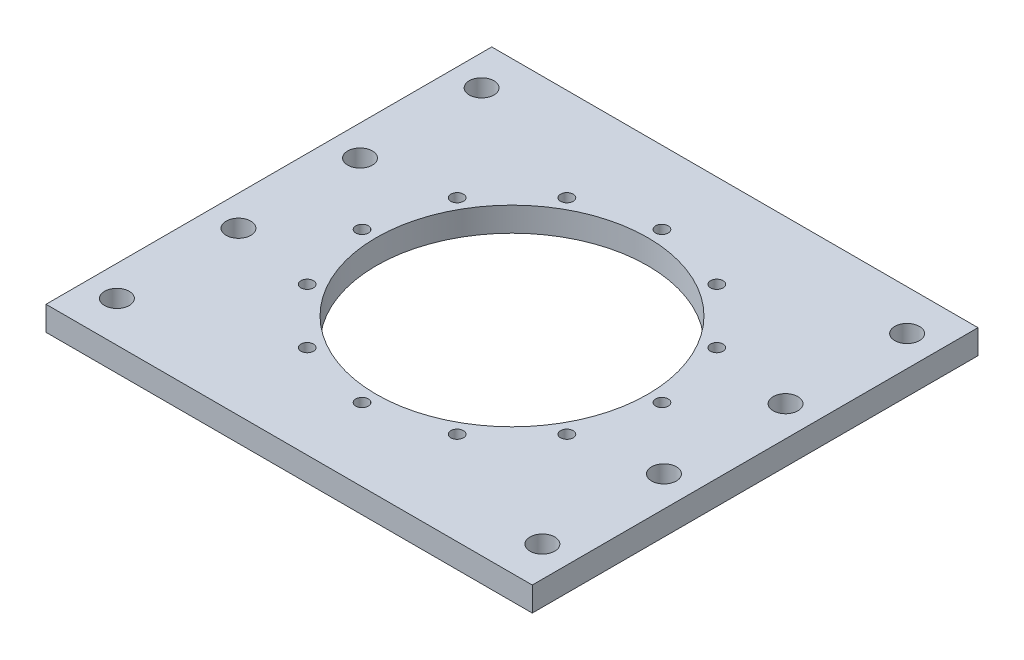
SolidWorks part; units mm, degrees
ref_plane "Front Plane" through (0, 0, 0) normal (0, 0, 1) x (1, 0, 0)
ref_plane "Top Plane" through (0, 0, 0) normal (0, 1, 0) x (1, 0, 0)
ref_plane "Right Plane" through (0, 0, 0) normal (1, 0, 0) x (0, 0, -1)
sketch "Sketch1" plane through (0, 0, 0) normal (0, 1, 0) x (1, 0, 0)
  line L1 (-60, 55) -> (60, 55)
  line L2 (-60, 55) -> (-60, -55)
  line L3 (-60, -55) -> (60, -55)
  line L4 (60, 55) -> (60, -55)
  line L5 (-60, 55) -> (60, -55) construction
  line L6 (-60, -55) -> (60, 55) construction
  point P0 (0, 0)
  dimension "D1" = 120
  dimension "D2" = 110
extrude "Boss-Extrude1" add sketch "Sketch1" along normal blind 6
sketch "Sketch2" plane through (0, 6, 0) normal (0, 1, 0) x (1, 0, 0)
  circle A2 centre (0, 0) radius 33.5
  dimension "D1" = 67
extrude "Cut-Extrude1" cut sketch "Sketch2" against normal through all
sketch "Sketch3" plane through (0, 6, 0) normal (0, 1, 0) x (1, 0, 0)
  point P0 (0, 37)
  dimension "D1" = 37
hole_wizard "M3 Clearance Hole1" positions "Sketch3" profile "Sketch4" hole size "M3" standard "ANSI Metric" end condition through all
sketch "Sketch4" plane through (0, 6, -37) normal (1, 0, 0) x (0, 0, 1)
  line L0 (0, 0) -> (0, 6)
  line L1 (0, 6) -> (1.55, 6)
  line L2 (1.55, 6) -> (1.55, 0)
  line L5 (1.55, 0) -> (0, 0)
  line L11 (0, -6.35) -> (0, 107.95) construction
  dimension "Thru Hole Dia." = 3.1
  dimension "Thru Hole Depth" = 6
pattern_circular "CirPattern1" count 12 over 360 about axis through (0, 0, 0) along (0, 1, 0) of "M3 Clearance Hole1"
sketch "Sketch5" plane through (0, 6, 0) normal (0, 1, 0) x (1, 0, 0)
  line L0 (-60, -55) -> (60, -55) construction
  line L1 (60, -55) -> (60, 55) construction
  line L2 (60, 55) -> (-60, 55) construction
  point P0 (52.5, -45)
  point P5 (52.5, -15)
  point P6 (52.5, 15)
  point P7 (52.5, 45)
  dimension "D1" = 10
  dimension "D2" = 7.5
  dimension "D3" = 10
  dimension "D4" = 30
  dimension "D5" = 90
  dimension "D6" = 30
hole_wizard "M6 Clearance Hole2" positions "Sketch5" profile "Sketch6" hole size "M6" standard "ANSI Metric" end condition through all
sketch "Sketch6" plane through (52.5, 6, 45) normal (1, 0, 0) x (0, 0, 1)
  line L0 (0, 0) -> (0, 6)
  line L1 (0, 6) -> (3.05, 6)
  line L2 (3.05, 6) -> (3.05, 0)
  line L5 (3.05, 0) -> (0, 0)
  line L11 (0, -6.35) -> (0, 107.95) construction
  dimension "Thru Hole Dia." = 6.1
  dimension "Thru Hole Depth" = 6
mirror "Mirror1" about plane through (0, 0, 0) normal (1, 0, 0) of "M6 Clearance Hole2"
equation "\"D3@Sketch5\"=\"D1@Sketch5\""
equation "\"D4@Sketch5\"=\"D5@Sketch5\"/3"
equation "\"D6@Sketch5\"=\"D5@Sketch5\"/3"
